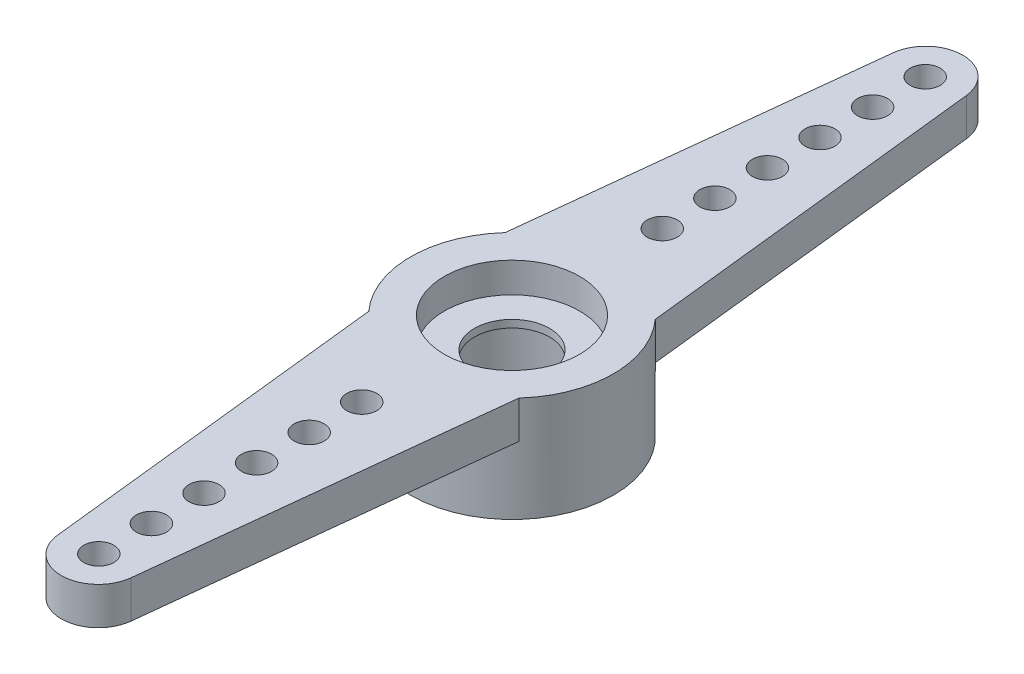
SolidWorks part; units mm, degrees
ref_plane "Front Plane" through (0, 0, 0) normal (0, 0, 1) x (1, 0, 0)
ref_plane "Top Plane" through (0, 0, 0) normal (0, 1, 0) x (1, 0, 0)
ref_plane "Right Plane" through (0, 0, 0) normal (1, 0, 0) x (0, 0, -1)
sketch "Sketch1" plane through (0, 0, 0) normal (0, 1, 0) x (1, 0, 0)
  circle A0 centre (0, 0) radius 2.286
  circle A1 centre (0, 0) radius 3.429
  dimension "D1" = 4.572
  dimension "D2" = 6.858
extrude "Boss-Extrude1" add sketch "Sketch1" along normal blind 3.556
sketch "Sketch2" plane through (0, 3.556, 0) normal (0, 1, 0) x (1, 0, 0)
  line L0 (0, 0) -> (0, 15.24) construction
  line L1 (-2.54, 2.3036) -> (-1.2445, 14.1244)
  line L2 (2.54, 2.3036) -> (1.2445, 14.1244)
  circle A0 centre (0, 0) radius 3.429 construction
  arc A1 (-1.2445, 14.1244) -> (0, 15.24) centre (0, 13.988) cw
  arc A2 (1.2445, 14.1244) -> (0, 15.24) centre (0, 13.988) ccw
  circle A3 centre (0, 0) radius 1.27
  circle A4 centre (0, 0) radius 2.286
  circle A5 centre (0, 0) radius 3.429
  circle M3 centre (0, 0) radius 3.429
  circle M4 centre (0, 0) radius 2.286
  dimension "D3" = 2.54
  dimension "D1" = 15.24
  dimension "D2" = 5.08
extrude "Boss-Extrude2" add sketch "Sketch2" against normal blind 1.27 contours A5 L0 A1 L1 | L0 L2 A2 M3 region at (-0.9605, 3.556, -8.3292) region at (0.9605, 3.556, -8.3292)
extrude "Boss-Extrude3" add sketch "Sketch2<3>" against normal blind 0.254 from offset 1.016 contours A3 M4 region at (-2.2213, 3.556, 0) offset against normal yes
sketch "Sketch2<3>" plane through (0, 3.556, 0) normal (0, 1, 0) x (1, 0, 0) same geometry as "Sketch2"
sketch "Sketch3" plane through (0, 3.556, 0) normal (0, 1, 0) x (1, 0, 0)
  line L0 (0, 0) -> (0, 15.24) construction
  circle A0 centre (0, 5.08) radius 0.508
  circle A1 centre (0, 5.08) radius 0.508
  circle A2 centre (0, 5.08) radius 0.508
  circle A3 centre (0, 5.08) radius 0.508
  circle A4 centre (0, 5.08) radius 0.508
  circle A5 centre (0, 5.08) radius 0.508
  dimension "D1" = 1.016
  dimension "D3" = 5.08
  dimension "D2" = 6
extrude "Cut-Extrude1" cut sketch "Sketch3" against normal through all contours A0 region at (0, 3.556, -5.08)
pattern_linear "LPattern1" count 6 spacing 1.778 along (0, 0, -1) of "Cut-Extrude1"
sketch "Sketch4" plane through (0, 0, 0) normal (1, 0, 0) x (0, 0, -1)
  line L1 (0, 0) -> (-4.3269, 0)
  line L2 (0, 0) -> (0, 6.7242)
  line L3 (0, 6.7242) -> (-4.3269, 6.7242)
  line L4 (-4.3269, 0) -> (-4.3269, 6.7242)
extrude "Cut-Extrude2" cut sketch "Sketch4" against normal through all both and the other way through all
mirror "Mirror1" about plane through (0, 0, 0) normal (0, 0, 1) of bodies 107
